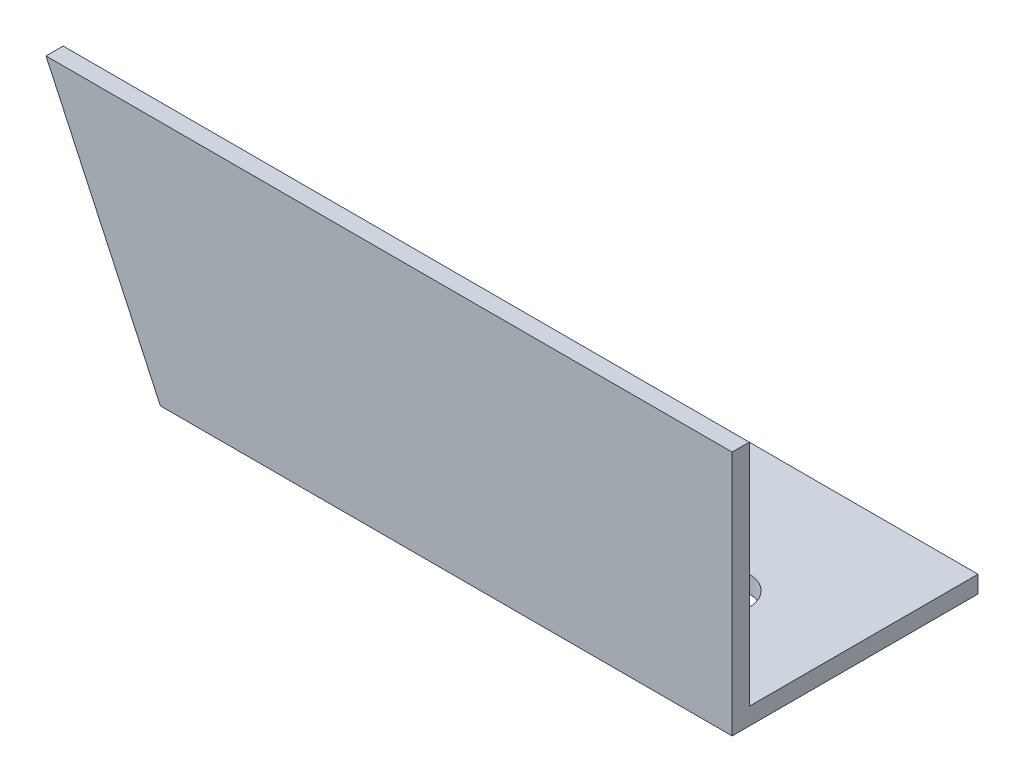
SolidWorks part; units mm, degrees
ref_plane "Спереди" through (0, 0, 0) normal (0, 0, 1) x (1, 0, 0)
ref_plane "Сверху" through (0, 0, 0) normal (0, 1, 0) x (1, 0, 0)
ref_plane "Справа" through (0, 0, 0) normal (1, 0, 0) x (0, 0, -1)
sketch "Эскиз1" plane through (0, 0, 0) normal (1, 0, 0) x (0, 0, -1)
  line L0 (0, 40) -> (0, 0)
  line L1 (0, 0) -> (40, 0)
extrude "Вытянуть-Тонкостенный1" add sketch "Эскиз1" along normal blind 120 thin thin type one direction wall 3
sketch "Эскиз2" plane through (0, 0, 3) normal (0, 0, 1) x (1, 0, 0)
  line L0 (0, 40) -> (20, -3)
  line L1 (120, -3) -> (0, -3) construction
  line L2 (20, -3) -> (0, -3)
  line L3 (0, -3) -> (0, 40)
extrude "Вырез-Вытянуть1" cut sketch "Эскиз2" against normal blind 50
sketch "Эскиз3" plane through (0, -3, 0) normal (0, -1, 0) x (1, 0, 0)
  circle A0 centre (100, -15) radius 5
  point P2 (0, 0)
extrude "Вырез-Вытянуть2" cut sketch "Эскиз3" against normal blind 10
